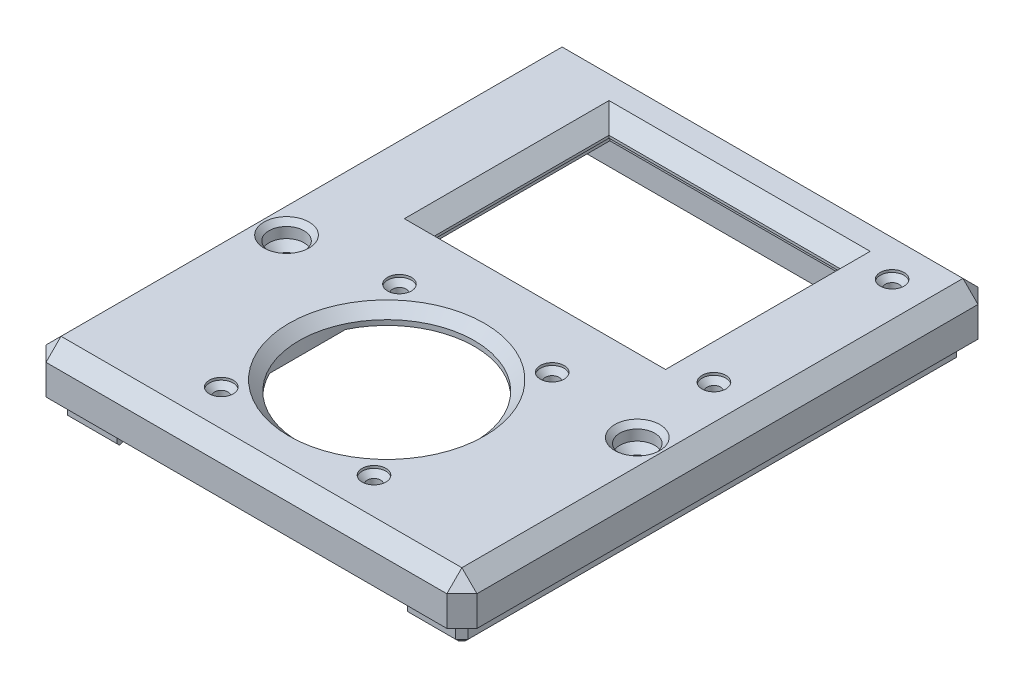
SolidWorks part; units mm, degrees
material "ABS"
ref_plane "Front Plane" through (0, 0, 0) normal (0, 0, 1) x (1, 0, 0)
ref_plane "Top Plane" through (0, 0, 0) normal (0, 1, 0) x (1, 0, 0)
ref_plane "Right Plane" through (0, 0, 0) normal (1, 0, 0) x (0, 0, -1)
sketch "Sketch1" plane through (0, 0, 0) normal (0, 1, 0) x (1, 0, 0)
  line L1 (43, 53) -> (-43, 53)
  line L2 (43, 53) -> (43, -53)
  line L3 (43, -53) -> (-43, -53)
  line L4 (-43, 53) -> (-43, -53)
  line L5 (43, 53) -> (-43, -53) construction
  line L6 (43, -53) -> (-43, 53) construction
  point P0 (0, 0)
  dimension "D1" = 86
  dimension "D2" = 106
extrude "Main Base" add sketch "Sketch1" along normal blind 9
sketch "Sketch2" plane through (0, 0, 0) normal (0, -1, 0) x (1, 0, 0)
  circle A0 centre (0, 25) radius 17.5
  dimension "D1" = 35
  dimension "D2" = 25
extrude "ANO Main Wheel Hole" cut sketch "Sketch2" against normal through all both and the other way through all
chamfer "ANO Main Wheel Hole Chamfer" distance 2 angle 45 1 edges at (0, 9, 7.5)
sketch "Sketch3" plane through (0, 0, 0) normal (0, -1, 0) x (1, 0, 0)
  line L0 (15.24, 7.22) -> (-15.24, 42.78) construction
  circle A0 centre (-15.24, 42.78) radius 1.35
  circle A1 centre (15.24, 42.78) radius 1.35
  circle A2 centre (15.24, 7.22) radius 1.35
  circle A3 centre (-15.24, 7.22) radius 1.35
  circle A4 centre (0, 25) radius 17.5 construction
  circle A5 centre (0, 25) radius 17.5 construction
  point P16 (0, 25)
  dimension "D1" = 2.7
  dimension "D2" = 30.48
  dimension "D3" = 35.56
extrude "ANO Mount Holes Cut" cut sketch "Sketch3" against normal through all and the other way through all
sketch "ANO Board Dimensions" plane through (0, 0, 0) normal (0, -1, 0) x (1, 0, 0)
  line L0 (-17.78, 7.22) -> (-17.78, 42.78)
  line L5 (-15.24, 45.32) -> (15.24, 45.32)
  line L6 (17.78, 42.78) -> (17.78, 7.22)
  line L7 (15.24, 4.68) -> (-15.24, 4.68)
  circle A0 centre (-15.24, 42.78) radius 2.54
  circle A1 centre (-15.24, 7.22) radius 2.54
  circle A2 centre (15.24, 7.22) radius 2.54
  circle A3 centre (15.24, 42.78) radius 2.54
  arc A5 (-17.78, 7.22) -> (-15.24, 4.68) centre (-15.24, 7.22) ccw
  arc A6 (17.78, 7.22) -> (15.24, 4.68) centre (15.24, 7.22) cw
  arc A7 (15.24, 45.32) -> (17.78, 42.78) centre (15.24, 42.78) cw
  arc A8 (-17.78, 42.78) -> (-15.24, 45.32) centre (-15.24, 42.78) cw
  dimension "D2" = 35.56
  dimension "D3" = 40.64
sketch "Sketch6" plane through (0, 0, 0) normal (0, -1, 0) x (1, 0, 0)
  line L0 (-17.78, 25) -> (-17.78, 37.7)
  line L1 (-17.78, 7.22) -> (-17.78, 42.78) construction
  line L2 (-15.24, 45.32) -> (15.24, 45.32) construction
  line L3 (-10.16, 45.32) -> (10.16, 45.32)
  line L4 (0, 25) -> (-17.78, 25) construction
  line L5 (0, 25) -> (0, 45.32) construction
  line L12 (17.78, 25) -> (17.78, 37.7)
  line L13 (-17.78, 25) -> (-17.78, 12.3)
  line L15 (-10.16, 4.68) -> (10.16, 4.68)
  line L16 (17.78, 12.3) -> (17.78, 25)
  arc A0 (-17.78, 37.7) -> (-15.24, 40.24) centre (-15.24, 37.7) cw
  circle A1 centre (-15.24, 42.78) radius 2.54 construction
  arc A2 (-15.24, 40.24) -> (-12.7, 42.78) centre (-15.24, 42.78) ccw
  arc A3 (-12.7, 42.78) -> (-10.16, 45.32) centre (-10.16, 42.78) cw
  arc A13 (17.78, 37.7) -> (15.24, 40.24) centre (15.24, 37.7) ccw
  arc A14 (15.24, 40.24) -> (12.7, 42.78) centre (15.24, 42.78) cw
  arc A15 (12.7, 42.78) -> (10.16, 45.32) centre (10.16, 42.78) ccw
  arc A16 (-17.78, 12.3) -> (-15.24, 9.76) centre (-15.24, 12.3) ccw
  arc A17 (-15.24, 9.76) -> (-12.7, 7.22) centre (-15.24, 7.22) cw
  arc A18 (-12.7, 7.22) -> (-10.16, 4.68) centre (-10.16, 7.22) ccw
  arc A19 (10.16, 4.68) -> (12.7, 7.22) centre (10.16, 7.22) ccw
  arc A20 (12.7, 7.22) -> (15.24, 9.76) centre (15.24, 7.22) cw
  arc A21 (15.24, 9.76) -> (17.78, 12.3) centre (15.24, 12.3) ccw
  circle A22 centre (-15.24, 7.22) radius 1.35 construction
  circle A23 centre (15.24, 7.22) radius 1.35 construction
  point P14 (0, 25)
  point P48 (0, 25)
extrude "ANO Board Offset Cut" cut sketch "Sketch6" against normal offset from surface (6 mm away) 3 up to face at (-15.24, 9, 5.87)
sketch "Sketch12" plane through (0, 0, 0) normal (0, -1, 0) x (1, 0, 0)
  line L0 (15.24, 4.68) -> (-15.24, 4.68) construction
  line L5 (17.78, 42.78) -> (17.78, 7.22) construction
  line L6 (-15.24, 45.32) -> (15.24, 45.32) construction
  line L7 (-17.78, 7.22) -> (-17.78, 42.78) construction
  line L20 (15.24, 4.68) -> (-15.24, 4.68) construction
  line L21 (17.78, 42.78) -> (17.78, 7.22) construction
  line L22 (-15.24, 45.32) -> (15.24, 45.32) construction
  line L23 (-17.78, 7.22) -> (-17.78, 42.78) construction
  line L24 (18.28, 42.78) -> (18.28, 7.22)
  line L25 (-15.24, 45.82) -> (15.24, 45.82)
  line L26 (-18.28, 7.22) -> (-18.28, 42.78)
  line L27 (15.24, 4.18) -> (-15.24, 4.18)
  arc A3 (-17.78, 42.78) -> (-15.24, 45.32) centre (-15.24, 42.78) cw construction
  arc A4 (17.78, 42.78) -> (15.24, 45.32) centre (15.24, 42.78) ccw construction
  arc A5 (-17.78, 7.22) -> (-15.24, 4.68) centre (-15.24, 7.22) ccw construction
  arc A6 (15.24, 4.68) -> (17.78, 7.22) centre (15.24, 7.22) ccw construction
  arc A7 (15.24, 4.18) -> (18.28, 7.22) centre (15.24, 7.22) ccw
  arc A8 (18.28, 42.78) -> (15.24, 45.82) centre (15.24, 42.78) ccw
  arc A9 (-18.28, 42.78) -> (-15.24, 45.82) centre (-15.24, 42.78) cw
  arc A10 (-18.28, 7.22) -> (-15.24, 4.18) centre (-15.24, 7.22) ccw
  dimension "D1" = 0.5
extrude "ANO Board Insert Cut" cut sketch "Sketch12" against normal offset from surface (4 mm away) 5 up to face at (-15.24, 9, 5.87)
chamfer "ANO Offset Chamfer" distance 2 angle 45 16 edges at (-11.9561, 6, 44.5761) (-13.4439, 6, 40.9839) (-17.0361, 6, 39.4961) (17.78, 6, 25) (11.9561, 6, 5.4239) (0, 6, 4.68) (13.4439, 6, 9.0161) (-11.9561, 6, 5.4239) (17.0361, 6, 10.5039) (-13.4439, 6, 9.0161) (-17.0361, 6, 10.5039) (17.0361, 6, 39.4961) (-17.78, 6, 25) (13.4439, 6, 40.9839) (11.9561, 6, 44.5761) (0, 6, 45.32)
chamfer "ANO Board Insert Chamfer" distance 4 angle 45 8 edges at (0, 0, 4.18) (17.3896, 0, 5.0704) (-17.3896, 0, 5.0704) (18.28, 0, 25) (-18.28, 0, 25) (17.3896, 0, 44.9296) (-17.3896, 0, 44.9296) (0, 0, 45.82)
sketch "Sketch7" plane through (0, 9, 0) normal (0, 1, 0) x (1, 0, 0)
  circle A0 centre (-15.24, -7.22) radius 2.375
  circle A1 centre (-15.24, -42.78) radius 2.375
  circle A2 centre (15.24, -42.78) radius 2.375
  circle A3 centre (15.24, -7.22) radius 2.375
  dimension "D1" = 4.75
extrude "ANO Screw Countersink Cut" cut sketch "Sketch7" against normal blind 2.5
chamfer "ANO Screw Countersink Chamfer" distance 2 angle 45 4 edges at (-15.24, 6.5, 45.155) (15.24, 6.5, 45.155) (15.24, 6.5, 9.595) (-15.24, 6.5, 9.595)
sketch "Sketch8" plane through (0, 9, 0) normal (0, 1, 0) x (1, 0, 0)
  line L1 (23.06, 42.42) -> (-23.06, 42.42)
  line L2 (23.06, 42.42) -> (23.06, 7.58)
  line L3 (23.06, 7.58) -> (-23.06, 7.58)
  line L4 (-23.06, 42.42) -> (-23.06, 7.58)
  line L5 (23.06, 42.42) -> (-23.06, 7.58) construction
  line L6 (23.06, 7.58) -> (-23.06, 42.42) construction
  point P0 (0, 25)
  dimension "D1" = 46.12
  dimension "D2" = 34.84
  dimension "D3" = 25
extrude "Display Main Cut" cut sketch "Sketch8" against normal through all
chamfer "Display Chamfer" distance 3 angle 45 4 edges at (0, 9, -7.58) (23.06, 9, -25) (0, 9, -42.42) (-23.06, 9, -25)
sketch "Sketch9" plane through (0, 0, 0) normal (0, -1, 0) x (1, 0, 0)
  line L8 (-23.06, -42.42) -> (-23.06, -7.58) construction
  line L9 (-25.52, -4.95) -> (29.68, -4.95) construction
  line L10 (-25.52, -4.95) -> (-25.52, -45.05) construction
  line L11 (-25.52, -45.05) -> (29.68, -45.05) construction
  line L12 (29.68, -4.95) -> (29.68, -45.05) construction
  line L13 (-26.02, -4.45) -> (-26.02, -45.55)
  line L14 (-26.02, -45.55) -> (30.18, -45.55)
  line L15 (30.18, -4.45) -> (30.18, -45.55)
  line L16 (-26.02, -4.45) -> (30.18, -4.45)
  point P6 (-23.06, -25)
  point P7 (-25.52, -25)
  dimension "D1" = 55.2
  dimension "D2" = 40.1
  dimension "D3" = 2.46
  dimension "D4" = 0.5
extrude "Display Offset Cut" cut sketch "Sketch9" against normal offset from surface (5.5 mm away) 3.5 up to face at (0, 9, -25)
sketch "Sketch10" plane through (0, 0, 0) normal (0, -1, 0) x (1, 0, 0)
  line L0 (-23.06, -7.58) -> (-23.06, -42.42) construction
  line L1 (-31.025, -4.875) -> (36.225, -4.875) construction
  line L2 (-31.025, -4.875) -> (-31.025, -45.125) construction
  line L3 (-31.025, -45.125) -> (36.225, -45.125) construction
  line L4 (36.225, -4.875) -> (36.225, -45.125) construction
  line L6 (-25.52, -4.95) -> (-25.52, -45.05) construction
  line L7 (33.08, -42.78) -> (-27.88, -7.22) construction
  line L8 (-27.88, -42.78) -> (33.08, -7.22) construction
  line L9 (-31.025, -25) -> (36.225, -25) construction
  circle A0 centre (-27.88, -7.22) radius 1.35 construction
  circle A1 centre (-27.88, -42.78) radius 1.35 construction
  circle A2 centre (33.08, -42.78) radius 1.35
  circle A3 centre (33.08, -7.22) radius 1.35
  point P6 (-23.06, -25)
  point P7 (-31.025, -25)
  point P18 (2.6, -25)
  point P23 (2.6, -25)
  dimension "D6" = 2.7
  dimension "D1" = 67.25
  dimension "D2" = 40.25
  dimension "D3" = 5.505
  dimension "D4" = 60.96
  dimension "D5" = 35.56
extrude "Display Mount Holes Cut" cut sketch "Sketch10" against normal through all
sketch "Sketch14" plane through (0, 0, 0) normal (0, -1, 0) x (1, 0, 0)
  circle A0 centre (-27.88, -7.22) radius 1.225
  circle A1 centre (-27.88, -42.78) radius 1.225
  dimension "D1" = 2.45
extrude "Display Secondary Mount Holes" cut sketch "Sketch14" against normal offset from surface (6 mm away) 3 up to face at (33.08, 9, -44.13)
sketch "Sketch11" plane through (0, 9, 0) normal (0, 1, 0) x (1, 0, 0)
  circle A0 centre (-27.88, 7.22) radius 2.375 construction
  circle A1 centre (-27.88, 42.78) radius 2.375 construction
  circle A2 centre (33.08, 42.78) radius 2.375
  circle A3 centre (33.08, 7.22) radius 2.375
  dimension "D1" = 4.75
extrude "Display Screw Countersink" cut sketch "Sketch11" against normal blind 2.5
chamfer "Display Screw Countersink Chamfer" distance 2 angle 45 2 edges at (33.08, 6.5, -40.405) (33.08, 6.5, -4.845)
sketch "Sketch13" plane through (0, 0, 0) normal (0, -1, 0) x (1, 0, 0)
  line L8 (36.725, -45.625) -> (36.725, -4.375)
  line L9 (-31.525, -45.625) -> (36.725, -45.625)
  line L10 (-31.525, -4.375) -> (-31.525, -45.625)
  line L11 (36.725, -4.375) -> (-31.525, -4.375)
  line L12 (36.725, -45.625) -> (36.725, -4.375)
  line L13 (-31.525, -45.625) -> (36.725, -45.625)
  line L14 (-31.525, -4.375) -> (-31.525, -45.625)
  line L15 (36.725, -4.375) -> (-31.525, -4.375)
  dimension "D1" = 0.5
extrude "Display Surface Offset Cut" cut sketch "Sketch13" against normal offset from surface (2 mm away) 7 contours L12 L15 L14 L13 up to face at (33.08, 9, -40.405)
chamfer "Display Back Chamfer" distance 2 angle 45 4 edges at (36.725, 0, -25) (2.6, 0, -45.625) (-31.525, 0, -25) (2.6, 0, -4.375)
sketch "Sketch16" plane through (0, 2, 0) normal (0, -1, 0) x (1, 0, 0)
  line L0 (30.18, -4.45) -> (30.18, -45.55) construction
  line L1 (36.725, -13.765) -> (36.725, -36.235)
  line L2 (36.725, -4.375) -> (36.725, -45.625) construction
  line L3 (30.18, -4.45) -> (30.18, -45.55) construction
  line L4 (30.18, -7.22) -> (30.18, -42.78)
  arc A0 (30.18, -7.22) -> (33.08, -10.12) centre (33.08, -7.22) ccw
  arc A1 (30.18, -42.78) -> (33.08, -39.88) centre (33.08, -42.78) cw
  arc A2 (33.08, -10.12) -> (36.725, -13.765) centre (33.08, -13.765) cw
  arc A3 (33.08, -39.88) -> (36.725, -36.235) centre (33.08, -36.235) ccw
extrude "Display Wire Spacer Cut" cut sketch "Sketch16" against normal up to surface (3.5 mm away) up to face at (2.08, 5.5, -25)
chamfer "Front Face Edge Chamfer" distance 3 angle 45 8 edges at (-43, 4.5, -53) (43, 4.5, -53) (-43, 4.5, 53) (43, 4.5, 53) (0, 9, 53) (-43, 9, 0) (0, 9, -53) (43, 9, 0)
sketch "Sketch19" plane through (0, 0, 0) normal (0, -1, 0) x (1, 0, 0)
  line L0 (0, -1000) -> (0, 49000) construction
  line L1 (38.7574, 50) -> (40, 48.7574)
  line L2 (28.1136, 50) -> (38.7574, 50)
  line L3 (30, 42.78) -> (30, 10)
  line L4 (40, 48.7574) -> (40, 10)
  line L9 (-30, 42.78) -> (-30, 10)
  line L16 (-40, 48.7574) -> (-40, -48.7574)
  line L17 (-40, -48.7574) -> (-38.7574, -50)
  line L18 (-38.7574, -50) -> (38.7574, -50)
  line L19 (38.7574, -50) -> (40, -48.7574)
  line L20 (40, -48.7574) -> (40, 48.7574)
  line L21 (40, 48.7574) -> (38.7574, 50)
  line L22 (38.7574, 50) -> (-38.7574, 50)
  line L23 (-38.7574, 50) -> (-40, 48.7574)
  line L24 (-40, 48.7574) -> (-40, 10)
  line L30 (-28.1136, 50) -> (-38.7574, 50)
  line L31 (-38.7574, 50) -> (-40, 48.7574)
  arc A1 (-15.24, 49.82) -> (-22.28, 42.78) centre (-15.24, 42.78) ccw construction
  arc A2 (-40, 10) -> (-30, 10) centre (-35, 10) ccw
  arc A3 (-28.1136, 50) -> (-30, 42.78) centre (-15.24, 42.78) ccw
  arc A4 (28.1136, 50) -> (30, 42.78) centre (15.24, 42.78) cw
  arc A5 (40, 10) -> (30, 10) centre (35, 10) cw
  dimension "D2" = 10
  dimension "D4" = 35
  dimension "D1" = 3
extrude "Screw Seat Lip Extrude" add sketch "Sketch19" along normal blind 5
sketch "Sketch20" plane through (0, 0, 0) normal (0, -1, 0) x (1, 0, 0)
  line L5 (38.7574, -48) -> (-37.9289, -48)
  line L6 (-37.9289, -48) -> (-38.5858, -47.3431)
  line L7 (-38.5858, -47.3431) -> (-38.5858, 6.5154)
  line L8 (38.7574, -48) -> (38.7574, 6.7012)
  line L10 (40, 50) -> (40, -48.7574)
  line L11 (40, -48.7574) -> (38.7574, -50)
  line L12 (-40, -48.7574) -> (-40, 50)
  line L13 (-38.7574, -50) -> (-40, -48.7574)
  line L14 (38.7574, -50) -> (-38.7574, -50)
  line L15 (40, 10) -> (40, -48.7574)
  line L16 (40, -48.7574) -> (38.7574, -50)
  line L17 (-40, -48.7574) -> (-40, 10)
  line L18 (-38.7574, -50) -> (-40, -48.7574)
  line L19 (38.7574, -50) -> (-38.7574, -50)
  arc A0 (-40, 10) -> (-30, 10) centre (-35, 10) ccw construction
  arc A1 (-40, 10) -> (-38.5858, 6.5154) centre (-35, 10) ccw
  arc A2 (30, 10) -> (40, 10) centre (35, 10) ccw construction
  arc A3 (38.7574, 6.7012) -> (40, 10) centre (35, 10) ccw
  dimension "D1" = 3
  dimension "D2" = 2
extrude "Seat Lip Edge Extrude" add sketch "Sketch20" along normal up to surface (5 mm away) up to face at (-34.5558, -5, 34.4431)
chamfer "Seat Lip Entry Chamfer" distance 1 angle 45 11 edges at (-28.1136, -2.5, 50) (28.1136, -2.5, 50) (-33.4355, -5, 50) (-39.3787, -5, 49.3787) (-40, -5, 0) (-39.3787, -5, -49.3787) (0, -5, -50) (39.3787, -5, -49.3787) (40, -5, 0) (39.3787, -5, 49.3787) (33.4355, -5, 50)
chamfer "Seat Lip Inner Chamfer" distance 1 angle 45 13 edges at (29.6523, -5, 45.965) (33.2374, -5, 5.321) (33.2374, 0, 5.321) (30, 0, 26.39) (30, -5, 26.39) (29.6097, 0, 46.152) (-38.5858, 0, -20.4139) (-33.1197, 0, 5.367) (-29.6429, 0, 46.0072) (-30, 0, 26.39) (-33.1197, -5, 5.367) (-30, -5, 26.39) (-29.6523, -5, 45.965)
chamfer "Seat Lip Base Chamfer" distance 1 angle 45 9 edges at (-33.8028, 0, 50) (-39.3787, 0, 49.3787) (-40, 0, 0) (-39.3787, 0, -49.3787) (0, 0, -50) (39.3787, 0, -49.3787) (40, 0, 0) (39.3787, 0, 49.3787) (33.9355, 0, 50)
sketch "Sketch21" plane through (0, -5, 0) normal (0, -1, 0) x (1, 0, 0)
  circle A0 centre (-35, 10) radius 2.1
  circle A1 centre (35, 10) radius 2.1
  dimension "D1" = 4.2
extrude "Box Mounting Hole Cut" cut sketch "Sketch21" against normal through all
sketch "Sketch22" plane through (0, 9, 0) normal (0, 1, 0) x (1, 0, 0)
  circle A0 centre (-35, -10) radius 3.5
  circle A1 centre (35, -10) radius 3.5
  dimension "D1" = 7
extrude "Box Mounting Hole Countersink" cut sketch "Sketch22" against normal blind 3
chamfer "Box Mounting Hole Chamfer" distance 1 angle 45 2 edges at (-35, 9, 13.5) (35, 9, 13.5)
chamfer "Box Mounting Hole Print Chamfer" distance 1.5 angle 45 2 edges at (35, 6, 12.1) (-35, 6, 12.1)
equation "\"ButtonSurfaceOffset\"= 5"
equation "\"D1@ANO Board Insert Cut\"=\"ButtonSurfaceOffset\""
equation "\"WallThickness\"= 9"
equation "\"D1@Main Base\"=\"WallThickness\""
equation "\"D1@ANO Board Offset Cut\"=\"ButtonSpacerCut\""
equation "\"ButtonSpacerCut\"= \"ButtonSurfaceOffset\" - \"ButtonBoardSpace\""
equation "\"D1@ANO Offset Chamfer\"=\"ButtonBoardSpace\""
equation "\"D1@ANO Board Insert Chamfer\"=\"WallThickness\"-\"ButtonSurfaceOffset\""
equation "\"ButtonBoardSpace\"= 2"
equation "\"DisplaySurfaceOffset\"= 2"
equation "\"D1@Display Offset Cut\"=\"WallThickness\"-\"DisplaySurfaceOffset\"-3.5"
equation "\"D1@Display Surface Offset Cut\" = \"WallThickness\" - \"DisplaySurfaceOffset\""
equation "\"D1@Display Back Chamfer\"=\"DisplaySurfaceOffset\""
